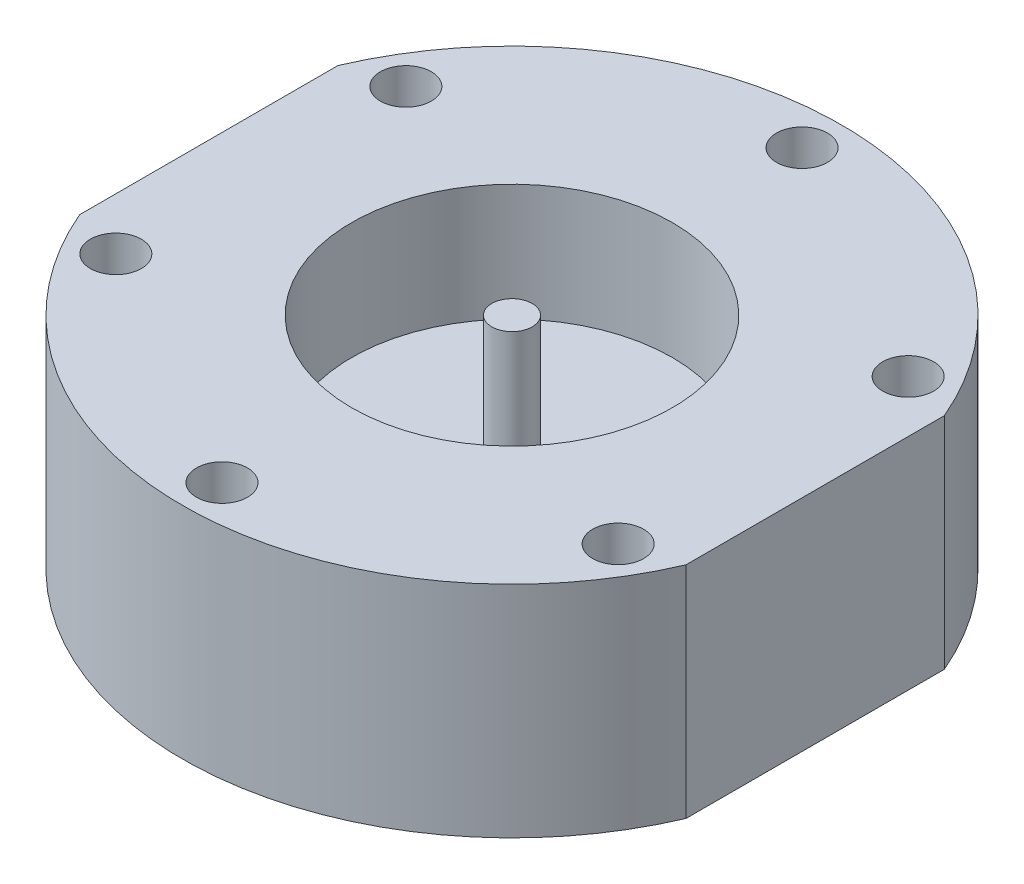
SolidWorks part; units mm, degrees
material "Copper"
ref_plane "Front Plane" through (0, 0, 0) normal (0, 0, 1) x (1, 0, 0)
ref_plane "Top Plane" through (0, 0, 0) normal (0, 1, 0) x (1, 0, 0)
ref_plane "Right Plane" through (0, 0, 0) normal (1, 0, 0) x (0, 0, -1)
ref_axis "Y Axis" through (0, 6.6675, 0) along (0, -1, 0)
sketch "outer" plane through (0, 0, 0) normal (0, 1, 0) x (1, 0, 0)
  circle A0 centre (0, 0) radius 19.05
  dimension "D1" = 38.1
extrude "Body" add sketch "outer" along normal blind 12.7
sketch "inner" plane through (0, 0, 0) normal (0, 1, 0) x (1, 0, 0)
  circle A0 centre (0, 0) radius 11.938
  dimension "D1" = 23.876
extrude "Pocket" cut sketch "inner" along normal blind 3.81
sketch "Screw Position" plane through (0, 0, 0) normal (0, 1, 0) x (1, 0, 0)
  point P0 (0, 16.764)
  dimension "D1" = 16.764
hole_wizard "#4 Clearance Hole1" positions "Sketch7" profile "Sketch8" hole size "#4" standard "ANSI Inch" end condition through all
sketch "Sketch7" plane through (0, 12.7, 0) normal (0, 1, 0) x (1, 0, 0)
  point P0 (0, 16.764)
sketch "Sketch8" plane through (0, 12.7, -16.764) normal (1, 0, 0) x (0, 0, 1)
  line L0 (0, 0) -> (0, 12.7)
  line L1 (0, 12.7) -> (1.4732, 12.7)
  line L2 (1.4732, 12.7) -> (1.4732, 0)
  line L5 (1.4732, 0) -> (0, 0)
  line L11 (0, -6.35) -> (0, 107.95) construction
  dimension "Thru Hole Dia." = 2.9464
  dimension "Thru Hole Depth" = 12.7
pattern_circular "Screw Holes" count 6 over 360 about axis through (0, 6.6675, 0) along (0, -1, 0) of "#4 Clearance Hole1"
sketch "Post Sketch" plane through (0, 0, 0) normal (0, 1, 0) x (1, 0, 0)
  circle A1 centre (3.81, 5.842) radius 2.413
  dimension "D1" = 3.81
  dimension "D4" = 4.826
extrude "Post" add sketch "Post Sketch" against normal blind 4.572 from surface starting at face at (0, 3.81, 11.938)
pattern_circular "Posts" count 4 over 360 about axis through (0, 6.6675, 0) along (0, -1, 0) of "Post"
sketch "Cut Sketch" plane through (0, 0, 0) normal (0, 1, 0) x (1, 0, 0)
  line L0 (-17.526, -19.05) -> (-20.574, -19.05)
  line L1 (17.526, 19.05) -> (20.574, 19.05)
  line L2 (17.526, 19.05) -> (17.526, -19.05)
  line L3 (17.526, -19.05) -> (20.574, -19.05)
  line L4 (20.574, 19.05) -> (20.574, -19.05)
  line L5 (17.526, 19.05) -> (20.574, -19.05) construction
  line L6 (17.526, -19.05) -> (20.574, 19.05) construction
  line L7 (-17.526, -19.05) -> (-17.526, 19.05)
  line L8 (-17.526, 19.05) -> (-20.574, 19.05)
  line L9 (-20.574, -19.05) -> (-20.574, 19.05)
  line L10 (-17.526, -19.05) -> (-20.574, 19.05) construction
  line L11 (-17.526, 19.05) -> (-20.574, -19.05) construction
  circle A0 centre (0, 0) radius 19.05 construction
  point P0 (19.05, 0)
  point P9 (-19.05, 0)
  point P14 (0, 0)
  dimension "D1" = 38.1
  dimension "D2" = 3.048
  dimension "D3" = 2
extrude "Flat Cut" cut sketch "Cut Sketch" against normal through all and the other way through all
sketch "Solenoid Pocket Sketch" plane through (0, 0, 0) normal (0, 1, 0) x (1, 0, 0)
  circle A0 centre (0, 0) radius 9.271
  circle A1 centre (0, 0) radius 1.1684
  dimension "D1" = 18.542
  dimension "D2" = 2.3368
extrude "Solenoid Pocket" cut sketch "Solenoid Pocket Sketch" against normal blind 6.7564 from surface starting at face at (0, 12.7, 0)
equation "\"outer_d\"= 3 / 2in"
equation "\"top_h\"= 0.5in"
equation "\"screw_r\"= 0.66in"
equation "\"inner_d\"= 0.94in"
equation "\"inner_h\"= 150mil"
equation "\"D1@outer\" = \"outer_d\""
equation "\"D1@Body\" = \"top_h\""
equation "\"D1@inner\"=\"inner_d\""
equation "\"D1@Pocket\" = \"inner_h\""
equation "\"D1@Screw Position\"=\"screw_r\""
equation "\"post_x\"= 0.15in"
equation "\"post_z\"= 0.23in"
equation "\"post_bottom_h\"= 0.03in"
equation "\"post_size\"= 0.190in"
equation "\"D1@Post\" = \"inner_h\" + \"post_bottom_h\""
equation "\"cut\"= 0.06in"
equation "\"D1@Cut Sketch\"=\"outer_d\""
equation "\"D2@Cut Sketch\"=2 * \"cut\""
equation "\"D1@Post Sketch\"=\"post_x\""
equation "\"D4@Post Sketch\"=\"post_size\""
equation "\"D2@Post Sketch\"=\"post_z\""
equation "\"solenoid_d\"= 0.73in"
equation "\"solenoid_h\"= 0.266in"
equation "\"solenoid_center_d\"= 0.092in"
equation "\"D1@Solenoid Pocket Sketch\" = \"solenoid_d\""
equation "\"D2@Solenoid Pocket Sketch\" = \"solenoid_center_d\""
equation "\"D1@Solenoid Pocket\"=\"solenoid_h\""
